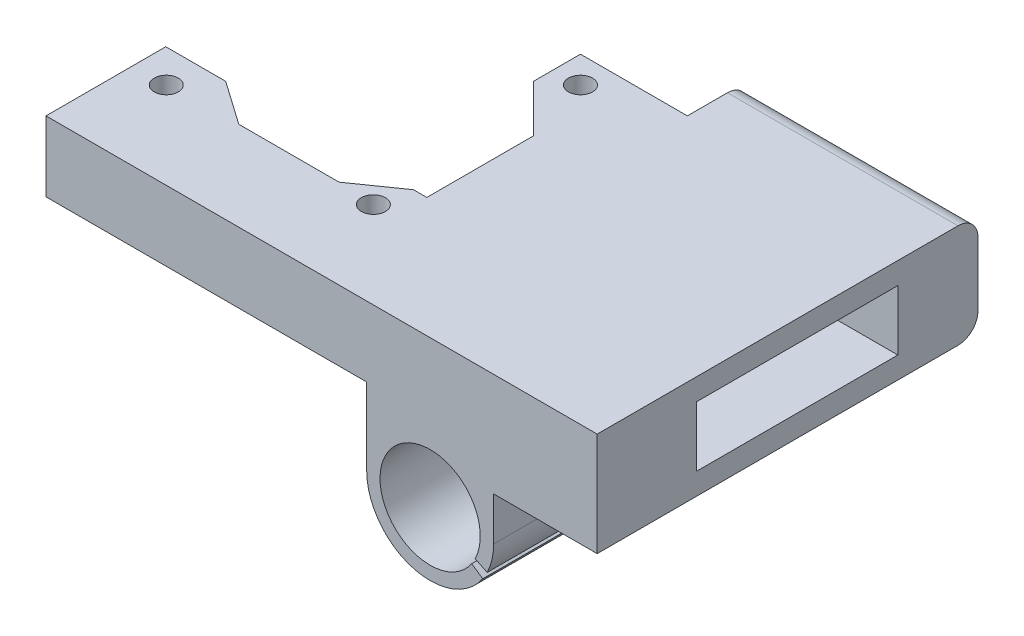
SolidWorks part; units mm, degrees
ref_plane "Front Plane" through (0, 0, 0) normal (0, 0, 1) x (1, 0, 0)
ref_plane "Top Plane" through (0, 0, 0) normal (0, 1, 0) x (1, 0, 0)
ref_plane "Right Plane" through (0, 0, 0) normal (1, 0, 0) x (0, 0, -1)
sketch "Sketch1" plane through (0, 0, 0) normal (0, 1, 0) x (1, 0, 0)
  line L0 (0, 0) -> (82.5, 0)
  line L1 (82.5, 0) -> (82.5, 57)
  line L2 (82.5, 57) -> (48, 57)
  line L3 (48, 57) -> (48, 48)
  line L4 (48, 48) -> (32, 48)
  line L5 (32, 48) -> (32, 41)
  line L6 (32, 41) -> (39.0711, 33.9289)
  line L7 (39.0711, 33.9289) -> (39.0711, 17.9289)
  line L8 (39.0711, 17.9289) -> (37.0711, 17.9289)
  line L9 (37.0711, 17.9289) -> (30.5179, 13.3403)
  line L10 (30.5179, 13.3403) -> (15.5179, 13.3403)
  line L11 (15.5179, 13.3403) -> (8.9646, 17.9289)
  line L12 (8.9646, 17.9289) -> (0, 17.9289)
  line L13 (0, 17.9289) -> (0, 0)
  line L14 (36, 44) -> (36, 13) construction
  line L15 (36, 13) -> (5, 13) construction
  circle A0 centre (5, 13) radius 1.8
  circle A1 centre (36, 13) radius 1.8
  circle A2 centre (36, 44) radius 1.8
  dimension "D16" = 3.6
  dimension "D18" = 13
  dimension "D19" = 5
  dimension "D1" = 82.5
  dimension "D2" = 57
  dimension "D3" = 34.5
  dimension "D4" = 9
  dimension "D5" = 16
  dimension "D6" = 7
  dimension "D7" = 10
  dimension "D8" = 135
  dimension "D9" = 16
  dimension "D10" = 2
  dimension "D11" = 8
  dimension "D12" = 145
  dimension "D13" = 15
  dimension "D14" = 8
  dimension "D15" = 145
  dimension "D17" = 31
extrude "Boss-Extrude1" add sketch "Sketch1" along normal blind 31.5 contours L12 L13 L0 L1 L2 L3 L4 L5 L6 L7 L8 L9 L10 L11 A2 A1 A0 region at (52.7105, 0, -24.1718)
sketch "Sketch2" plane through (0, 0, 0) normal (0, -1, 0) x (1, 0, 0)
  line L0 (82.5, -57) -> (82.5, 0)
  line L1 (82.5, 0) -> (67, 0)
  line L2 (0, 0) -> (82.5, 0) construction
  line L3 (67, 0) -> (67, -48)
  line L4 (67, -48) -> (48, -48)
  line L5 (48, -48) -> (48, -57)
  line L6 (82.5, -57) -> (48, -57) construction
  line L7 (48, -57) -> (82.5, -57)
  dimension "D1" = 15.5
extrude "Cut-Extrude1" cut sketch "Sketch2" against normal blind 16
fillet "Fillet1" radius 3 2 edges at (65.25, 31.5, -57) (65.25, 16, -57)
sketch "Sketch3" plane through (0, 0, -48) normal (0, 0, -1) x (-1, 0, 0)
  line L0 (-67, 0) -> (-32, 0) construction
  line L1 (-67, 16) -> (-67, 0) construction
  line L2 (-64.241, 6.2122) -> (-66.0385, 5.3355)
  line L3 (-67, 0) -> (-48, 0)
  line L4 (-67, 0) -> (-67, 16)
  line L5 (-67, 16) -> (-48, 16)
  line L6 (-48, 0) -> (-48, 16)
  line L7 (-65.3759, 4.1877) -> (-63.7178, 5.3061)
  line L8 (-64.241, 6.2122) -> (-57.5, 9.5) construction
  line L9 (-57.5, 9.5) -> (-57.5, 0) construction
  circle A0 centre (-57.5, 9.5) radius 9.5
  circle A1 centre (-57.5, 9.5) radius 7.5
  line M1 (-67, 0) -> (-32, 0)
  line M5 (-48, 16) -> (-67, 16)
  dimension "D1" = 19
  dimension "D2" = 15
  dimension "D3" = 8
  dimension "D4" = 64
extrude "Cut-Extrude2" cut sketch "Sketch3" against normal through all both and the other way through all contours A1 M5 | A1 M5 | A0 L4 M1 | A1 L2 A0 L7 | A0 L3 L6 region at (64.8892, 5.2339, -48) region at (57.5, 9.2966, -48) region at (64.878, 2.122, -48) region at (57.5, 16.4024, -48) region at (50.122, 2.122, -48)
sketch "Sketch5" plane through (0, 0, 0) normal (0, -1, 0) x (1, 0, 0)
  line L1 (48, -48) -> (0, -48)
  line L2 (48, -48) -> (48, 0)
  line L3 (48, 0) -> (0, 0)
  line L4 (0, -48) -> (0, 0)
extrude "Cut-Extrude3" cut sketch "Sketch5" against normal blind 21
sketch "Sketch6" plane through (82.5, 0, 0) normal (1, 0, 0) x (0, 0, -1)
  line L0 (45, 23.75) -> (57, 23.75) construction
  line L1 (14.858, 28.25) -> (45, 28.25)
  line L2 (14.858, 28.25) -> (14.858, 19.25)
  line L3 (14.858, 19.25) -> (45, 19.25)
  line L4 (45, 28.25) -> (45, 19.25)
  line L6 (57, 28.5) -> (57, 19) construction
  dimension "D1" = 9
  dimension "D2" = 30.142
  dimension "D3" = 12
extrude "Cut-Extrude4" cut sketch "Sketch6" against normal blind 31.4
sketch "Sketch7" plane through (51.1, 0, 0) normal (1, 0, 0) x (0, 0, -1)
  line L0 (14.858, 19.25) -> (45, 19.25) construction
  line L3 (17.9289, 19.25) -> (38.9289, 19.25)
  line L4 (17.9289, 19.25) -> (17.9289, 28.25)
  line L7 (17.9289, 28.25) -> (38.9289, 28.25)
  line L8 (38.9289, 19.25) -> (38.9289, 28.25)
  line L9 (45, 28.25) -> (14.858, 28.25) construction
  point P4 (0, 0)
  point P7 (18.9185, 19)
  point P10 (0, 0)
  dimension "D1" = 21
extrude "Cut-Extrude5" cut sketch "Sketch7" against normal through all
sketch "Sketch8" plane through (0, 21, 0) normal (0, -1, 0) x (1, 0, 0)
  circle A0 centre (5, -13) radius 3.5
  circle A1 centre (36, -13) radius 3.5
  circle A2 centre (36, -44) radius 3.5
  dimension "D1" = 7
extrude "Cut-Extrude6" cut sketch "Sketch8" against normal blind 1.5
